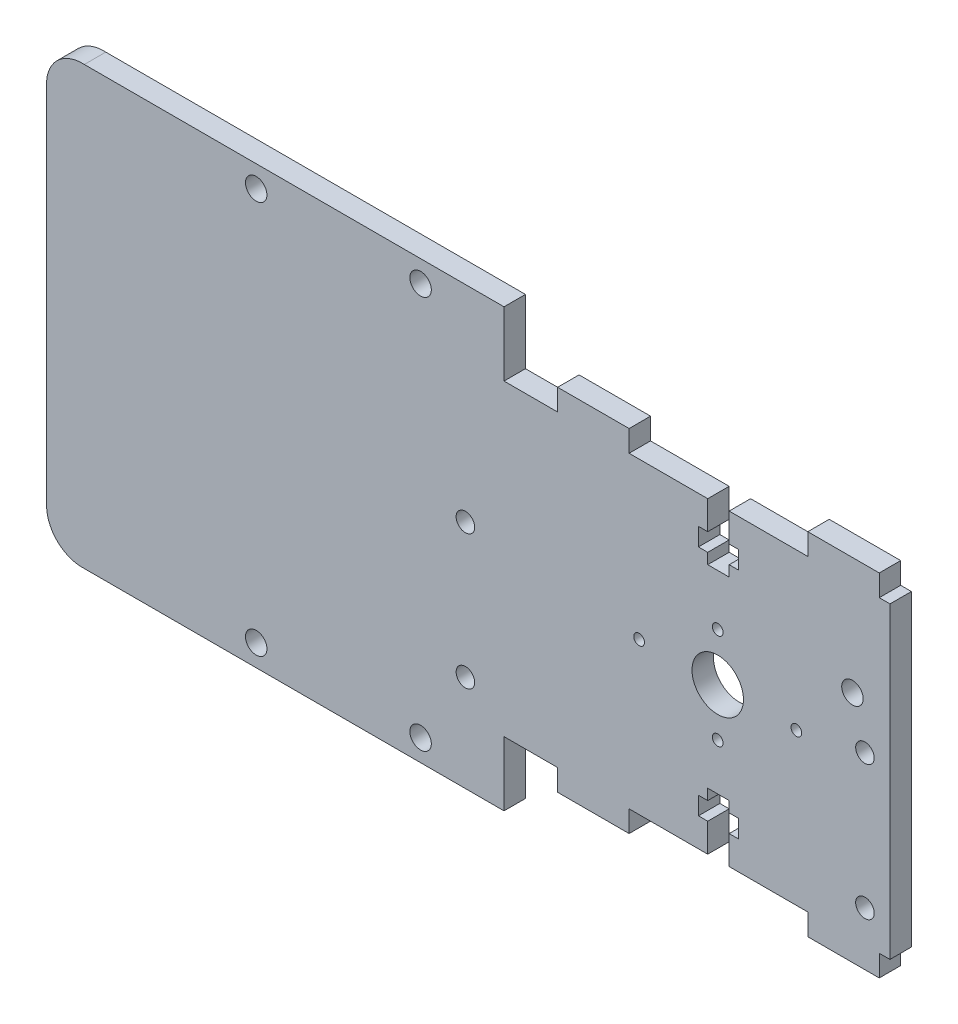
SolidWorks part; units mm, degrees
ref_plane "Front Plane" through (0, 0, 0) normal (0, 0, 1) x (1, 0, 0)
ref_plane "Top Plane" through (0, 0, 0) normal (0, 1, 0) x (1, 0, 0)
ref_plane "Right Plane" through (0, 0, 0) normal (1, 0, 0) x (0, 0, -1)
sketch "Model" plane through (0, 0, 0) normal (0, 0, 1) x (1, 0, 0)
  line L1 (88.808, 39.598) -> (4.308, 39.598) construction
  line L4 (43.808, 64.448) -> (43.808, 61.448)
  line L6 (43.808, 15.368) -> (43.808, 18.368)
  line L7 (53.808, 15.368) -> (43.808, 15.368)
  line L8 (53.808, 18.368) -> (53.808, 15.368)
  line L9 (64.808, 18.368) -> (53.808, 18.368)
  line L10 (64.808, 22.368) -> (64.808, 18.368)
  line L11 (63.508, 22.368) -> (64.808, 22.368)
  line L12 (63.508, 24.868) -> (63.508, 22.368)
  line L13 (64.808, 24.868) -> (63.508, 24.868)
  line L14 (64.808, 26.368) -> (64.808, 24.868)
  line L15 (67.808, 26.368) -> (64.808, 26.368)
  line L16 (67.808, 24.868) -> (67.808, 26.368)
  line L17 (69.108, 24.868) -> (67.808, 24.868)
  line L18 (69.108, 22.368) -> (69.108, 24.868)
  line L19 (67.808, 22.368) -> (69.108, 22.368)
  line L20 (67.808, 18.368) -> (67.808, 22.368)
  line L21 (78.808, 18.368) -> (67.808, 18.368)
  line L22 (78.808, 15.368) -> (78.808, 18.368)
  line L23 (88.808, 15.368) -> (78.808, 15.368)
  line L24 (78.808, 64.448) -> (88.808, 64.448)
  line L25 (78.808, 61.448) -> (78.808, 64.448)
  line L26 (67.808, 61.448) -> (78.808, 61.448)
  line L27 (67.808, 57.4481) -> (67.808, 61.448)
  line L28 (69.108, 57.4481) -> (67.808, 57.4481)
  line L29 (69.108, 54.9481) -> (69.108, 57.4481)
  line L30 (67.808, 54.9481) -> (69.108, 54.9481)
  line L31 (67.808, 53.448) -> (67.808, 54.9481)
  line L32 (64.808, 53.448) -> (67.808, 53.448)
  line L33 (64.808, 54.9481) -> (64.808, 53.448)
  line L34 (63.508, 54.9481) -> (64.808, 54.9481)
  line L35 (63.508, 57.4481) -> (63.508, 54.9481)
  line L36 (64.808, 57.4481) -> (63.508, 57.4481)
  line L37 (64.808, 61.448) -> (64.808, 57.4481)
  line L38 (53.808, 61.448) -> (64.808, 61.448)
  line L39 (53.808, 64.448) -> (53.808, 61.448)
  line L40 (43.808, 64.448) -> (53.808, 64.448)
  line L41 (42.558, 48.068) -> (85.058, 48.068) construction
  line L42 (1.308, 39.6674) -> (55.2079, 39.5877) construction
  line L44 (88.808, 61.448) -> (90.308, 61.448)
  line L45 (90.308, 61.448) -> (90.308, 18.368)
  line L46 (90.308, 18.368) -> (88.808, 18.368)
  line L47 (88.808, 64.448) -> (88.808, 61.448)
  line L48 (88.808, 18.368) -> (88.808, 15.368)
  line L49 (30.908, 41.668) -> (86.808, 41.668) construction
  line L50 (30.908, 41.668) -> (30.908, 22.868) construction
  line L51 (30.908, 22.868) -> (86.808, 22.868) construction
  line L52 (66.208, 46.298) -> (66.208, 39.598) construction
  line L53 (36.308, 61.448) -> (36.308, 70.448)
  line L54 (36.308, 70.448) -> (-22.4142, 70.448)
  line L55 (36.308, 18.368) -> (36.308, 9.368)
  line L56 (36.308, 9.368) -> (-22.4142, 9.368)
  line L57 (43.808, 61.448) -> (36.308, 61.448)
  line L58 (43.808, 18.368) -> (36.308, 18.368)
  line L59 (-27.6928, 14.3602) -> (-27.6928, 65.743)
  line L60 (1.6358, 67.408) -> (24.6358, 67.408) construction
  line L61 (1.6358, 67.408) -> (1.6358, 12.408) construction
  line L62 (1.6358, 12.408) -> (24.6358, 12.408) construction
  line L63 (24.6358, 12.408) -> (24.6358, 67.408) construction
  circle A0 centre (66.208, 39.598) radius 3.6
  circle A1 centre (66.208, 39.598) radius 3.6
  circle A2 centre (55.2079, 39.5877) radius 0.75
  circle A3 centre (66.208, 46.298) radius 0.75
  circle A4 centre (66.208, 32.898) radius 0.75
  circle A5 centre (77.208, 39.598) radius 0.75
  circle A7 centre (85.058, 48.068) radius 1.5
  arc A8 (-22.4142, 70.448) -> (-27.6928, 65.743) centre (-22.701, 65.4562) ccw
  arc A9 (-27.6928, 14.3602) -> (-22.4142, 9.368) centre (-22.6928, 14.3602) ccw
  circle A13 centre (30.908, 41.668) radius 1.3
  circle A14 centre (86.808, 41.668) radius 1.3
  circle A15 centre (30.908, 22.868) radius 1.3
  circle A16 centre (86.808, 22.868) radius 1.3
  circle A17 centre (1.6358, 67.408) radius 1.5
  circle A18 centre (24.6358, 67.408) radius 1.5
  circle A19 centre (1.6358, 12.408) radius 1.5
  circle A20 centre (24.6358, 12.408) radius 1.5
  dimension "D8" = 3
  dimension "D18" = 5.25
  dimension "D21" = 55.9
  dimension "D22" = 18.8
  dimension "D23" = 55.9
  dimension "D24" = 3.5
  dimension "D25" = 4.5
  dimension "D26" = 6.7
  dimension "D28" = 11.0001
  dimension "D29" = 11
  dimension "D33" = 23
  dimension "D35" = 3.04
  dimension "D1" = 3
  dimension "D2" = 10
  dimension "D3" = 3.9999
  dimension "D4" = 1.5
  dimension "D9" = 8
  dimension "D10" = 4
  dimension "D11" = 2.5
  dimension "D12" = 3
  dimension "D13" = 1.3
  dimension "D14" = 11
  dimension "D15" = 1.3
  dimension "D16" = 11
  dimension "D17" = 10
  dimension "D19" = 3
  dimension "D20" = 3
  dimension "D27" = 6.7
  dimension "D30" = 10
  dimension "D31" = 9
  dimension "D32" = 9
  dimension "D34" = 55
  dimension "D36" = 7.5
extrude "Boss-Extrude1" add sketch "Model" along normal blind 3 contours A9 L6 L7 L8 L9 L10 L11 L12 L13 L14 L15 L16 L17 L18 L19 L20 L21 L22 L23 L24 L25 L26 L27 L28 L29 L30 L31 L32 L33 L34 L35 L36 L37 L38 L39 L40 L4 A8 A0 A2 A3 region at (26.3648, 39.9275, 0)
